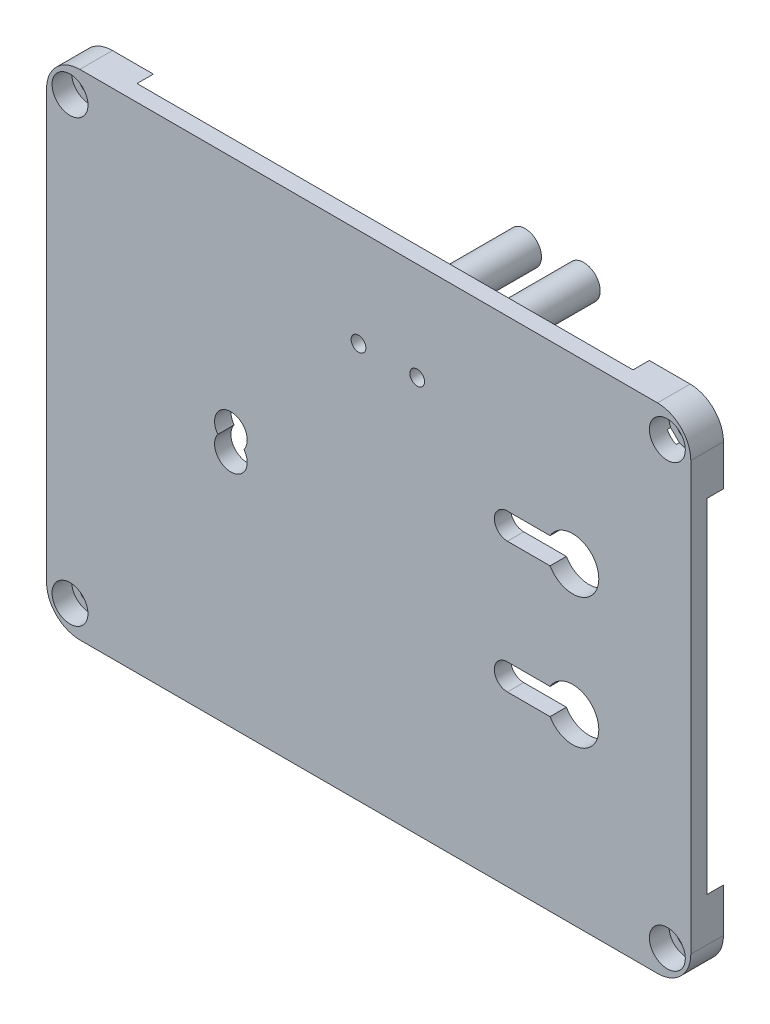
SolidWorks part; units mm, degrees
ref_plane "Front Plane" through (0, 0, 0) normal (0, 0, 1) x (1, 0, 0)
ref_plane "Top Plane" through (0, 0, 0) normal (0, 1, 0) x (1, 0, 0)
ref_plane "Right Plane" through (0, 0, 0) normal (1, 0, 0) x (0, 0, -1)
sketch "Sketch1" plane through (0, 0, 0) normal (0, 0, 1) x (1, 0, 0)
  line L23 (-90.972, -37.8425) -> (-2.5, -37.8425)
  line L24 (-96.072, 32.7425) -> (-96.072, -32.7425)
  line L25 (-2.5, 37.8425) -> (-90.972, 37.8425)
  line L26 (2.6, -32.7425) -> (2.6, 32.7425)
  line L27 (-90.972, -37.8425) -> (-2.5, -37.8425)
  line L28 (-96.072, 32.7425) -> (-96.072, -32.7425)
  line L29 (-2.5, 37.8425) -> (-90.972, 37.8425)
  line L30 (2.6, -32.7425) -> (2.6, 32.7425)
  arc A27 (-96.072, -32.7425) -> (-90.972, -37.8425) centre (-90.972, -32.7425) ccw
  arc A28 (-90.972, 37.8425) -> (-96.072, 32.7425) centre (-90.972, 32.7425) ccw
  arc A29 (2.6, 32.7425) -> (-2.5, 37.8425) centre (-2.5, 32.7425) ccw
  arc A30 (-2.5, -37.8425) -> (2.6, -32.7425) centre (-2.5, -32.7425) ccw
  arc A31 (-96.072, -32.7425) -> (-90.972, -37.8425) centre (-90.972, -32.7425) ccw
  arc A32 (-90.972, 37.8425) -> (-96.072, 32.7425) centre (-90.972, 32.7425) ccw
  arc A33 (2.6, 32.7425) -> (-2.5, 37.8425) centre (-2.5, 32.7425) ccw
  arc A34 (-2.5, -37.8425) -> (2.6, -32.7425) centre (-2.5, -32.7425) ccw
  dimension "D1" = 0.1
extrude "Boss-Extrude1" add sketch "Sketch1" along normal up to surface (5 mm away) contours L30 A33 L29 A32 L28 A31 L27 A34
sketch "Sketch3" plane through (0, 0, 0) normal (0, 0, -1) x (-1, 0, 0)
  line L0 (-2.6, -26.0571) -> (-2.6, 26.4856)
  line L1 (-2.6, -32.7425) -> (-2.6, 32.7425) construction
  line L2 (-2.6, 26.4856) -> (8.7569, 37.8425)
  line L3 (2.5, 37.8425) -> (90.972, 37.8425) construction
  line L4 (8.7569, 37.8425) -> (84.7178, 37.8425)
  line L5 (84.7178, 37.8425) -> (96.0747, 26.4856)
  line L6 (96.0747, 26.4856) -> (96.072, -26.0571)
  line L7 (96.072, 32.7425) -> (96.072, -32.7425) construction
  line L8 (96.072, -26.0571) -> (84.3643, -37.7648)
  line L9 (84.3643, -37.7648) -> (8.7569, -37.7648)
  line L10 (8.7569, -37.7648) -> (-2.6, -26.0571)
extrude "Cut-Extrude1" cut sketch "Sketch3" against normal offset from surface (2.5 mm away) 2.5 up to face at (-46.736, 0, 5)
sketch "Sketch4" plane through (0, 0, 5) normal (0, 0, 1) x (1, 0, 0)
  line L1 (-0.9915, -33.7293) -> (-92.4805, -33.7293) construction
  line L2 (-0.9915, -33.7293) -> (-0.9915, 33.7293) construction
  line L3 (-0.9915, 33.7293) -> (-92.4805, 33.7293) construction
  line L4 (-92.4805, -33.7293) -> (-92.4805, 33.7293) construction
  line L5 (-0.9915, -33.7293) -> (-92.4805, 33.7293) construction
  line L6 (-0.9915, 33.7293) -> (-92.4805, -33.7293) construction
  point P4 (-46.736, 0)
hole_wizard "CBORE for M3 SHCS1" positions "3DSketch1" profile "Sketch5" counterbore size "M3" standard "ANSI Metric" end condition through all
sketch3d "3DSketch1"
  point P0 (-0.9915, -33.7293, 5)
  point P3 (-0.9915, 33.7293, 5)
  point P6 (-92.4805, 33.7293, 5)
  point P9 (-92.4805, -33.7293, 5)
sketch "Sketch5" plane through (-0.9915, -33.7293, 5) normal (1, 0, 0) x (0, -1, 0)
  line L0 (0, 0) -> (0, 5)
  line L1 (0, 5) -> (1.6, 5)
  line L3 (1.6, 5) -> (1.6, 3)
  line L4 (1.6, 3) -> (2.75, 3)
  line L5 (2.75, 3) -> (2.75, 0)
  line L7 (2.75, 0) -> (0, 0)
  line L11 (0, -6.35) -> (0, 107.95) construction
  dimension "Thru Hole Dia." = 3.2
  dimension "Thru Hole Depth" = 5
  dimension "C'Bore Dia." = 5.5
  dimension "C'Bore Depth" = 3
sketch "Sketch6" plane through (0, 0, 5) normal (0, 0, 1) x (1, 0, 0)
  line L0 (-41.0793, 22.7965) -> (-37.5279, 22.7965) construction
  line L1 (-50.0723, 22.7965) -> (-46.5209, 22.7965) construction
  circle A0 centre (-39.3036, 22.7965) radius 1.8275 construction
  circle A1 centre (-48.2966, 22.7965) radius 1.8297 construction
  circle A2 centre (-48.2966, 22.7965) radius 2.5297
  circle A3 centre (-39.3036, 22.7965) radius 2.5275
  circle A4 centre (-48.2966, 22.7965) radius 1.1297
  circle A5 centre (-39.3036, 22.7965) radius 1.1275
  dimension "D1" = 0.7
  dimension "D2" = 0.7
extrude "Boss-Extrude2" add sketch "Sketch6" against normal blind 25.5 contours A3 A5 | A2 A4 region at (-50.7547, 22.7965, 5) region at (-41.7596, 22.7965, 5)
sketch "Sketch7" plane through (0, 0, 5) normal (0, 0, 1) x (1, 0, 0)
  line L0 (-96.072, 0) -> (2.6, 0) construction
  line L1 (-96.072, -32.7425) -> (-96.072, 32.7425) construction
  line L2 (2.6, 32.7425) -> (2.6, -32.7425) construction
  line L3 (-15.49, -10) -> (-25.49, -10) construction
  line L4 (-18.9541, -12) -> (-25.49, -12)
  line L5 (-18.9541, -8) -> (-25.49, -8)
  line L6 (-18.9541, -12) -> (-25.49, -12)
  line L7 (-18.9541, -8) -> (-25.49, -8)
  line L8 (-18.9541, -12) -> (-25.49, -12)
  line L9 (-18.9541, -8) -> (-25.49, -8)
  line L10 (-18.9541, -12) -> (-25.49, -12)
  line L11 (-18.9541, -8) -> (-25.49, -8)
  line L12 (-18.9541, 12) -> (-25.49, 12)
  line L13 (-18.9541, 8) -> (-25.49, 8)
  circle A0 centre (-39.3036, 22.7965) radius 1.1275
  circle A1 centre (-48.2966, 22.7965) radius 1.1297
  arc A3 (-25.49, -8) -> (-25.49, -12) centre (-25.49, -10) ccw
  arc A4 (-18.9541, -12) -> (-18.9541, -8) centre (-15.49, -10) ccw
  arc A5 (-18.9541, 12) -> (-18.9541, 8) centre (-15.49, 10) cw
  arc A6 (-25.49, 8) -> (-25.49, 12) centre (-25.49, 10) cw
  arc A7 (-65.8401, 0) -> (-69.8401, 0) centre (-67.8401, 1.5) ccw
  arc A8 (-69.8401, 0) -> (-65.8401, 0) centre (-67.8401, -1.5) ccw
  point P14 (-20.49, -10)
  point P32 (-64.3976, 0)
  dimension "D2" = 5
  dimension "D4" = 8
  dimension "D1" = 5
  dimension "D6" = 3
  dimension "D3" = 10
extrude "Cut-Extrude2" cut sketch "Sketch7" against normal through all contours L4 A4 L5 A3 | A6 L13 A5 L12 | A0 | A1 | A7 A8 region at (-18.4297, -10, 5) region at (-18.4297, 10, 5) region at (-39.3036, 22.7965, 5) region at (-48.2966, 22.7965, 5) region at (-67.8401, 0, 5)
